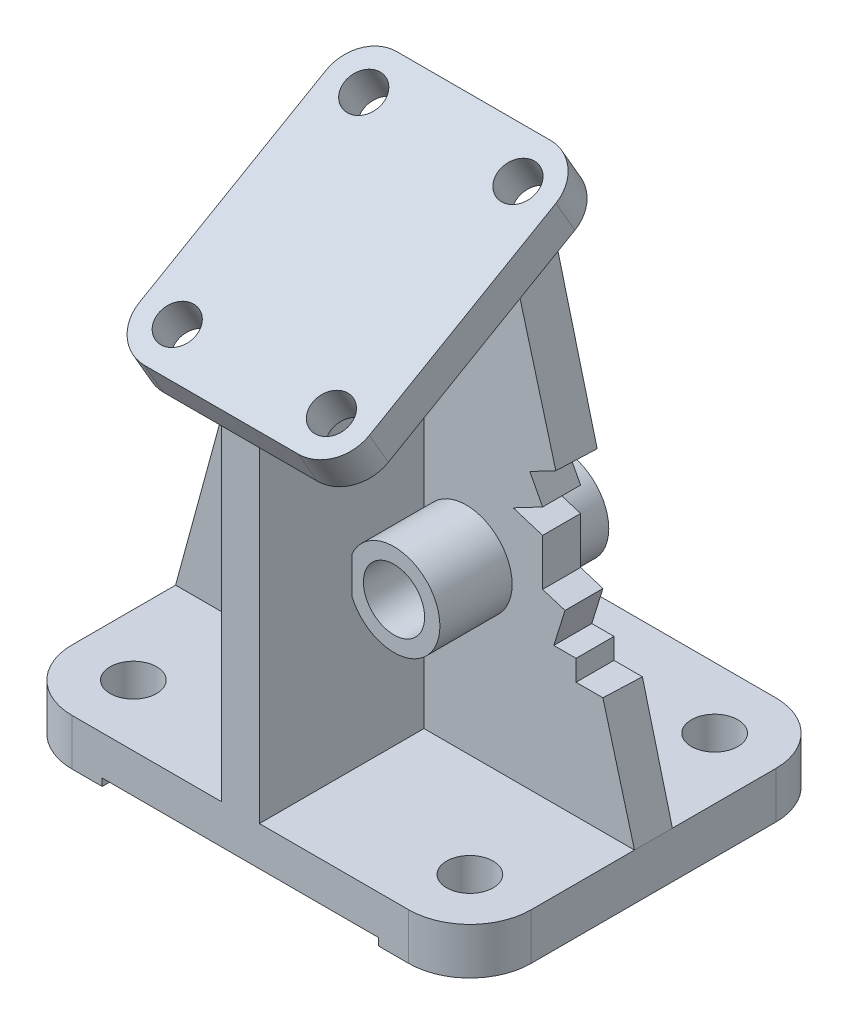
SolidWorks part; units mm, degrees
ref_plane "Alzado" through (0, 0, 0) normal (0, 0, 1) x (1, 0, 0)
ref_plane "Planta" through (0, 0, 0) normal (0, 1, 0) x (1, 0, 0)
ref_plane "Vista lateral" through (0, 0, 0) normal (1, 0, 0) x (0, 0, -1)
sketch "Croquis1" plane through (0, 0, 0) normal (0, 1, 0) x (1, 0, 0)
  line L1 (-34.925, 38.1) -> (34.925, 38.1)
  line L2 (-47.625, 25.4) -> (-47.625, -25.4)
  line L3 (-34.925, -38.1) -> (34.925, -38.1)
  line L4 (47.625, 25.4) -> (47.625, -25.4)
  line L5 (-47.625, 38.1) -> (47.625, -38.1) construction
  line L6 (-47.625, -38.1) -> (47.625, 38.1) construction
  arc A0 (-34.925, 38.1) -> (-47.625, 25.4) centre (-34.925, 25.4) ccw
  arc A1 (-47.625, -25.4) -> (-34.925, -38.1) centre (-34.925, -25.4) ccw
  arc A2 (34.925, -38.1) -> (47.625, -25.4) centre (34.925, -25.4) ccw
  arc A3 (34.925, 38.1) -> (47.625, 25.4) centre (34.925, 25.4) cw
  circle A4 centre (-34.925, 25.4) radius 4.826
  circle A5 centre (34.925, 25.4) radius 4.826
  circle A6 centre (-34.925, -25.4) radius 4.826
  circle A7 centre (34.925, -25.4) radius 4.826
  point P0 (0, 0)
  dimension "D3" = 12.7
  dimension "D4" = 9.652
  dimension "D1" = 95.25
  dimension "D2" = 76.2
extrude "Saliente-Extruir1" add sketch "Croquis1" along normal blind 9.652
sketch "Croquis2" plane through (0, 0, 38.1) normal (0, 0, 1) x (1, 0, 0)
  line L0 (-34.925, 0) -> (34.925, 0) construction
  line L1 (-28.702, 0) -> (28.702, 0)
  line L2 (-28.702, 0) -> (-28.702, 1.524)
  line L3 (-28.702, 1.524) -> (28.702, 1.524)
  line L4 (28.702, 0) -> (28.702, 1.524)
  line L5 (-34.925, 9.652) -> (34.925, 9.652) construction
  point P6 (0, 1.524)
  point P9 (0, 9.652)
  dimension "D1" = 1.524
  dimension "D2" = 28.702
extrude "Cortar-Extruir1" cut sketch "Croquis2" against normal through all
sketch "Croquis3" plane through (0, 0, 0) normal (1, 0, 0) x (0, 0, -1)
  line L0 (-38.1, 9.652) -> (-38.1, 77.216) construction
  line L1 (-38.1, 77.216) -> (14.253, 107.442) construction
  dimension "D1" = 67.564
  dimension "D2" = 60.452
  dimension "D3" = 30
ref_plane "Plano1" through (0, 74.4098, 42.9605) normal (0, -0.866, -0.5) x (0, 0.5, -0.866)
sketch "Croquis4" plane through (0, 74.4098, 42.9605) normal (0, -0.866, -0.5) x (0, 0.5, -0.866)
  line L0 (5.6124, 0) -> (66.0644, 0) construction
  line L1 (5.6124, 0) -> (66.0644, 0) construction
  line L3 (58.1904, -23.876) -> (13.4864, -23.876)
  line L4 (66.0644, -16.002) -> (66.0644, 16.002)
  line L5 (58.1904, 23.876) -> (13.4864, 23.876)
  line L6 (5.6124, -16.002) -> (5.6124, 16.002)
  line L7 (66.0644, -23.876) -> (5.6124, 23.876) construction
  line L8 (66.0644, 23.876) -> (5.6124, -23.876) construction
  arc A0 (66.0644, 16.002) -> (58.1904, 23.876) centre (58.1904, 16.002) ccw
  arc A1 (58.1904, -23.876) -> (66.0644, -16.002) centre (58.1904, -16.002) ccw
  arc A2 (13.4864, -23.876) -> (5.6124, -16.002) centre (13.4864, -16.002) cw
  arc A3 (13.4864, 23.876) -> (5.6124, 16.002) centre (13.4864, 16.002) ccw
  circle A4 centre (58.1904, -16.002) radius 3.937
  circle A6 centre (13.4864, 16.002) radius 3.937
  circle A7 centre (13.4864, -16.002) radius 3.937
  circle A8 centre (58.1904, 16.002) radius 3.937
  point P2 (35.8384, 0)
  point P7 (66.0644, 0)
  dimension "D2" = 7.874
  dimension "D3" = 7.874
  dimension "D1" = 47.752
extrude "Saliente-Extruir2" add sketch "Croquis4" against normal blind 7.874 separate body
sketch "Croquis5" plane through (0, 9.652, 0) normal (0, 1, 0) x (1, 0, 0)
  line L0 (-47.625, 25.4) -> (-47.625, -25.4) construction
  line L1 (-47.625, 3.937) -> (47.625, 3.937)
  line L2 (-47.625, 3.937) -> (-47.625, -3.937)
  line L3 (-47.625, -3.937) -> (-3.937, -3.937)
  line L4 (47.625, 3.937) -> (47.625, -3.937)
  line L5 (47.625, -25.4) -> (47.625, 25.4) construction
  line L6 (-34.925, -38.1) -> (34.925, -38.1) construction
  line L8 (-3.937, -3.937) -> (-3.937, -38.1)
  line L9 (-3.937, -38.1) -> (3.937, -38.1)
  line L10 (3.937, -3.937) -> (3.937, -38.1)
  line L11 (3.937, -3.937) -> (47.625, -3.937)
  point P15 (0, -38.1)
  dimension "D1" = 7.874
  dimension "D2" = 3.937
extrude "Saliente-Extruir3" add sketch "Croquis5" along normal up to surface (91.8341 mm away) up to face at (16.002, 83.1215, 27.8714)
sketch "Croquis6" plane through (0, 0, 3.937) normal (0, 0, 1) x (1, 0, 0)
  line L0 (23.876, 96.94) -> (47.625, 9.652)
  line L1 (47.625, 9.652) -> (47.625, 96.94)
  line L2 (47.625, 96.94) -> (23.876, 96.94)
sketch "Croquis7" plane through (0, 0, -3.937) normal (0, 0, -1) x (-1, 0, 0)
  line L0 (-23.876, 101.4861) -> (-47.625, 9.652)
  line L1 (-47.625, 9.652) -> (-47.625, 101.4861)
  line L2 (-47.625, 101.4861) -> (-23.876, 101.4861)
loft "Cortar-Recubrir2" cut profiles "Croquis6", "Croquis7" connector at (23.876, 96.94, 3.937) connector at (23.876, 101.4861, -3.937)
mirror "Simetría1" about plane through (0, 0, 0) normal (1, 0, 0) of "Cortar-Recubrir2"
sketch "Croquis8" plane through (0, 0, 3.937) normal (0, 0, 1) x (1, 0, 0)
  line L1 (3.937, 9.652) -> (47.625, 9.652) construction
  circle A0 centre (12.7, 44.704) radius 9.525
  circle A1 centre (12.7, 44.704) radius 6.35
  dimension "D3" = 19.05
  dimension "D4" = 12.7
  dimension "D1" = 12.7
  dimension "D2" = 35.052
extrude "Saliente-Extruir4" add sketch "Croquis8" against normal blind 35.052 from offset 14.986
extrude "Cortar-Extruir2" cut sketch "Croquis8<2>" against normal through all contours A1
sketch "Croquis8<2>" plane through (0, 0, 3.937) normal (0, 0, 1) x (1, 0, 0) same geometry as "Croquis8"
sketch "Croquis9" plane through (0, 0, 3.937) normal (0, 0, 1) x (1, 0, 0)
  line L0 (35.5011, 71.8827) -> (25.9062, 66.8454)
  line L1 (25.9062, 66.8454) -> (28.5593, 61.7917)
  line L2 (28.5593, 61.7917) -> (22.4621, 58.5906)
  line L3 (22.4621, 58.5906) -> (28.5593, 56.6915)
  line L4 (28.5593, 56.6915) -> (28.5593, 46.9768)
  line L5 (28.5593, 46.9768) -> (33.2085, 45.5287)
  line L6 (33.2085, 45.5287) -> (30.8839, 38.0655)
  line L7 (30.8839, 38.0655) -> (35.5011, 38.0655)
  line L8 (35.5011, 38.0655) -> (35.5011, 33.7544)
  line L9 (35.5011, 33.7544) -> (44.7247, 33.7544)
  line L10 (44.7247, 33.7544) -> (35.5011, 71.8827)
extrude "Cortar-Extruir3" cut sketch "Croquis9" against normal through all
